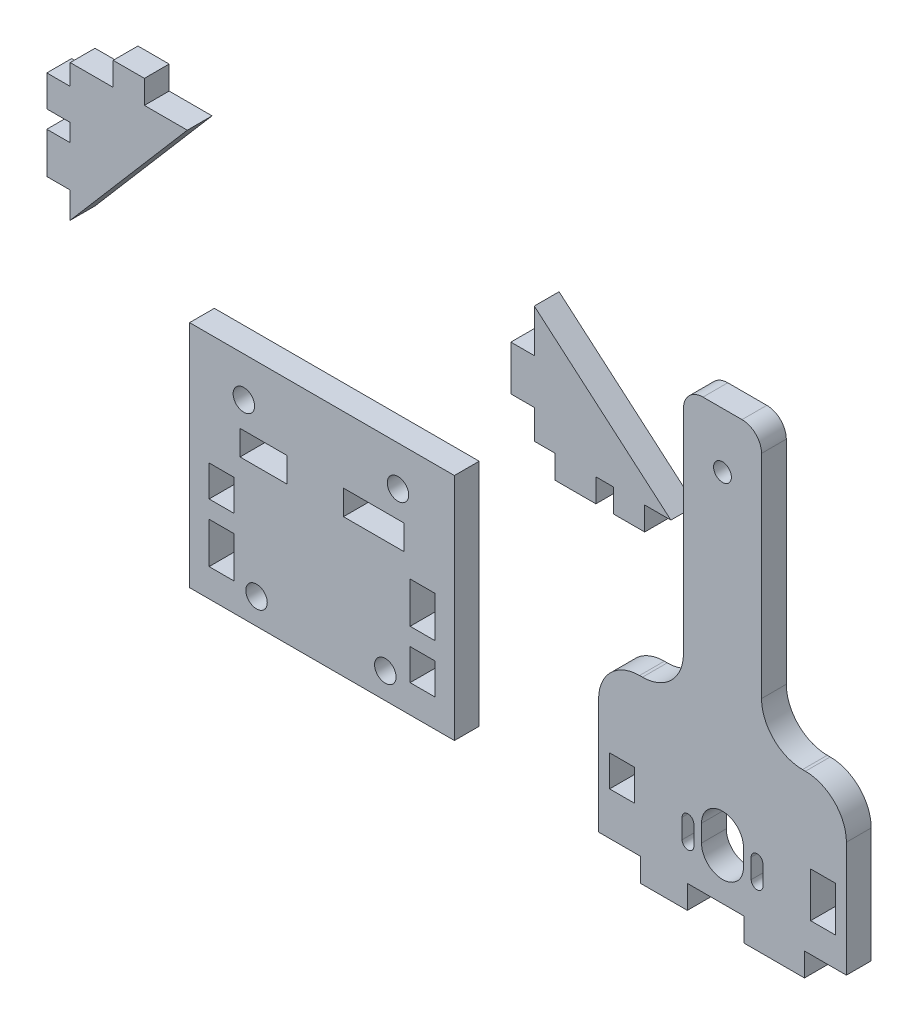
SolidWorks part; units mm, degrees
ref_plane "Front Plane" through (0, 0, 0) normal (0, 0, 1) x (1, 0, 0)
ref_plane "Top Plane" through (0, 0, 0) normal (0, 1, 0) x (1, 0, 0)
ref_plane "Right Plane" through (0, 0, 0) normal (1, 0, 0) x (0, 0, -1)
sketch "Model" plane through (0, 0, 0) normal (0, 0, 1) x (1, 0, 0)
  line L0 (46.0634, 150.8229) -> (46.0634, 142.8229)
  line L1 (46.0634, 138.3229) -> (46.0634, 127.8229)
  line L2 (52.0634, 156.1129) -> (52.0634, 150.8229)
  line L3 (52.0634, 142.8229) -> (52.0634, 138.3229)
  line L4 (52.0634, 127.8229) -> (52.0634, 121.1129)
  line L5 (63.0634, 162.1129) -> (63.0634, 156.1129)
  line L6 (52.0634, 121.1129) -> (82.0634, 156.1129)
  line L7 (71.0634, 156.1129) -> (71.0634, 162.1129)
  line L8 (71.6003, 124.5085) -> (71.6003, 132.5085)
  line L9 (86.6003, 129.5085) -> (86.6003, 124.5085)
  line L10 (87.649, 85.0685) -> (87.649, 77.0685)
  line L11 (87.649, 72.5685) -> (87.649, 62.0685)
  line L12 (93.999, 62.0685) -> (93.999, 72.5685)
  line L13 (93.999, 77.0685) -> (93.999, 85.0685)
  line L14 (95.574, 96.7035) -> (95.574, 90.3535)
  line L15 (198.1866, 47.05) -> (210.1866, 47.05)
  line L16 (224.6866, 47.05) -> (240.1866, 47.05)
  line L17 (187.4366, 53.05) -> (198.1866, 53.05)
  line L18 (210.1866, 53.05) -> (224.6866, 53.05)
  line L19 (240.1866, 53.05) -> (250.9366, 53.05)
  line L20 (107.574, 90.3535) -> (107.574, 96.7035)
  line L21 (63.2366, 54.8885) -> (169.9114, 54.8885)
  line L22 (248.1116, 60.55) -> (241.7616, 60.55)
  line L23 (87.649, 62.0685) -> (93.999, 62.0685)
  line L24 (139.149, 62.0685) -> (145.499, 62.0685)
  line L25 (190.2616, 64.05) -> (196.6116, 64.05)
  line L26 (145.499, 70.0685) -> (139.149, 70.0685)
  line L27 (248.1116, 72.05) -> (241.7616, 72.05)
  line L28 (196.6116, 72.05) -> (190.2616, 72.05)
  line L29 (93.999, 72.5685) -> (87.649, 72.5685)
  line L30 (145.499, 74.5685) -> (139.149, 74.5685)
  line L31 (122.074, 96.7035) -> (122.074, 90.3535)
  line L32 (87.649, 77.0685) -> (93.999, 77.0685)
  line L33 (145.499, 85.0685) -> (139.149, 85.0685)
  line L34 (93.999, 85.0685) -> (87.649, 85.0685)
  line L35 (129.624, 124.2585) -> (129.624, 131.2585)
  line L36 (137.574, 90.3535) -> (137.574, 96.7035)
  line L37 (139.149, 70.0685) -> (139.149, 62.0685)
  line L38 (139.149, 74.5685) -> (139.149, 85.0685)
  line L39 (95.574, 90.3535) -> (107.574, 90.3535)
  line L40 (122.074, 90.3535) -> (137.574, 90.3535)
  line L41 (240.4366, 93.05) -> (239.6866, 93.05)
  line L42 (198.6866, 93.05) -> (197.9366, 93.05)
  line L43 (140.624, 133.2585) -> (140.624, 124.2585)
  line L44 (145.499, 62.0685) -> (145.499, 70.0685)
  line L45 (145.499, 74.5685) -> (145.499, 85.0685)
  line L46 (137.574, 96.7035) -> (122.074, 96.7035)
  line L47 (107.574, 96.7035) -> (95.574, 96.7035)
  line L48 (164.9642, 139.0399) -> (164.9642, 150.5399)
  line L49 (140.624, 124.2585) -> (129.624, 124.2585)
  line L50 (86.6003, 124.5085) -> (71.6003, 124.5085)
  line L51 (176.2542, 125.5399) -> (186.7542, 125.5399)
  line L52 (191.2542, 125.5399) -> (199.2542, 125.5399)
  line L53 (170.9642, 161.5399) -> (170.9642, 150.5399)
  line L54 (170.9642, 139.0399) -> (170.9642, 131.5399)
  line L55 (176.2542, 131.5399) -> (176.2542, 125.5399)
  line L56 (46.0634, 127.8229) -> (52.0634, 127.8229)
  line L57 (170.9642, 131.5399) -> (176.2542, 131.5399)
  line L58 (186.7542, 131.5399) -> (191.2542, 131.5399)
  line L59 (199.2542, 131.5399) -> (205.9642, 131.5399)
  line L60 (71.6003, 132.5085) -> (83.6003, 132.5085)
  line L61 (131.624, 133.2585) -> (140.624, 133.2585)
  line L62 (186.7542, 131.5399) -> (186.7542, 125.5399)
  line L63 (187.4366, 82.55) -> (187.4366, 53.05)
  line L64 (190.2616, 72.05) -> (190.2616, 64.05)
  line L65 (191.2542, 131.5399) -> (191.2542, 125.5399)
  line L66 (52.0634, 138.3229) -> (46.0634, 138.3229)
  line L67 (170.9642, 139.0399) -> (164.9642, 139.0399)
  line L68 (46.0634, 142.8229) -> (52.0634, 142.8229)
  line L69 (196.6116, 64.05) -> (196.6116, 72.05)
  line L70 (198.1866, 53.05) -> (198.1866, 47.05)
  line L71 (199.2542, 125.5399) -> (199.2542, 131.5399)
  line L72 (170.9642, 150.5399) -> (164.9642, 150.5399)
  line L73 (52.0634, 150.8229) -> (46.0634, 150.8229)
  line L74 (82.0634, 156.1129) -> (71.0634, 156.1129)
  line L75 (63.0634, 156.1129) -> (52.0634, 156.1129)
  line L76 (208.8366, 67.05) -> (208.8366, 62.05)
  line L77 (209.1866, 157.95) -> (209.1866, 103.55)
  line L78 (210.1866, 47.05) -> (210.1866, 53.05)
  line L79 (211.8366, 62.05) -> (211.8366, 67.05)
  line L80 (71.0634, 162.1129) -> (63.0634, 162.1129)
  line L81 (224.1866, 162.95) -> (214.1866, 162.95)
  line L82 (205.9642, 131.5399) -> (170.9642, 161.5399)
  line L83 (212.8116, 68.2) -> (212.8116, 63.8)
  line L84 (224.6866, 53.05) -> (224.6866, 47.05)
  line L85 (225.5616, 63.8) -> (225.5616, 68.2)
  line L86 (226.5366, 67.05) -> (226.5366, 62.05)
  line L87 (229.1866, 103.55) -> (229.1866, 157.95)
  line L88 (229.5366, 62.05) -> (229.5366, 67.05)
  line L89 (240.1866, 47.05) -> (240.1866, 53.05)
  line L90 (241.7616, 60.55) -> (241.7616, 72.05)
  line L91 (248.1116, 60.55) -> (248.1116, 72.05)
  line L92 (250.9366, 53.05) -> (250.9366, 82.55)
  arc A0 (169.9114, 54.8885) -> (63.2366, 54.8885) centre (116.574, 92.0385) ccw
  arc A1 (229.1866, 103.55) -> (239.6866, 93.05) centre (239.6866, 103.55) ccw
  arc A2 (250.9366, 82.55) -> (240.4366, 93.05) centre (240.4366, 82.55) ccw
  arc A3 (197.9366, 93.05) -> (187.4366, 82.55) centre (197.9366, 82.55) ccw
  arc A4 (198.6866, 93.05) -> (209.1866, 103.55) centre (198.6866, 103.55) ccw
  arc A5 (225.5616, 68.2) -> (212.8116, 68.2) centre (219.1866, 68.2) ccw
  arc A6 (212.8116, 63.8) -> (225.5616, 63.8) centre (219.1866, 63.8) ccw
  arc A7 (214.1866, 162.95) -> (209.1866, 157.95) centre (214.1866, 157.95) ccw
  arc A8 (229.1866, 157.95) -> (224.1866, 162.95) centre (224.1866, 157.95) ccw
  arc A9 (86.6003, 129.5085) -> (83.6003, 132.5085) centre (83.6003, 129.5085) ccw
  circle A10 centre (219.1866, 148.81) radius 2.285
  circle A11 centre (78.574, 66.1385) radius 2.2
  circle A12 centre (154.574, 66.1385) radius 2.2
  circle A13 centre (83.574, 117.8885) radius 2.2
  circle A14 centre (149.574, 117.8885) radius 2.2
  arc A15 (131.624, 133.2585) -> (129.624, 131.2585) centre (131.624, 131.2585) ccw
  arc A16 (226.5366, 62.05) -> (229.5366, 62.05) centre (228.0366, 62.05) ccw
  arc A17 (229.5366, 67.05) -> (226.5366, 67.05) centre (228.0366, 67.05) ccw
  arc A18 (208.8366, 62.05) -> (211.8366, 62.05) centre (210.3366, 62.05) ccw
  arc A19 (211.8366, 67.05) -> (208.8366, 67.05) centre (210.3366, 67.05) ccw
extrude "Boss-Extrude1" add sketch "Model" along normal blind 6.35
sketch "Sketch2" plane through (0, 0, 6.35) normal (0, 0, 1) x (1, 0, 0)
  line L0 (219.1866, 68.2) -> (219.1866, 63.8) construction
  line L1 (224.5616, 68.2) -> (224.5616, 63.8)
  line L2 (213.8116, 68.2) -> (213.8116, 63.8)
  line L3 (225.5616, 63.8) -> (225.5616, 68.2) construction
  line L4 (219.1866, 68.2) -> (219.1866, 63.8) construction
  line L5 (226.1415, 68.2) -> (226.1415, 63.8)
  line L6 (212.2318, 68.2) -> (212.2318, 63.8)
  arc A0 (224.5616, 68.2) -> (213.8116, 68.2) centre (219.1866, 68.2) ccw
  arc A1 (213.8116, 63.8) -> (224.5616, 63.8) centre (219.1866, 63.8) ccw
  arc A2 (226.1415, 68.2) -> (212.2318, 68.2) centre (219.1866, 68.2) ccw
  arc A3 (212.2318, 63.8) -> (226.1415, 63.8) centre (219.1866, 63.8) ccw
  point P4 (219.1866, 66)
  point P13 (219.1866, 66)
  dimension "D1" = 1
extrude "Boss-Extrude2" add sketch "Sketch2" against normal up to surface (6.35 mm away) up to face at (244.9366, 66.3, 0)
sketch "Sketch4" plane through (0, 0, 6.35) normal (0, 0, 1) x (1, 0, 0)
  line L0 (63.2366, 54.8885) -> (169.9114, 54.8885) construction
  line L2 (82.649, 54.8885) -> (82.649, 113.7035)
  line L3 (82.649, 113.7035) -> (150.499, 113.7035)
  line L4 (150.499, 54.8885) -> (150.499, 113.7035)
  line L5 (87.649, 72.5685) -> (87.649, 62.0685) construction
  line L6 (145.499, 62.0685) -> (145.499, 70.0685) construction
  line L7 (137.574, 96.7035) -> (122.074, 96.7035) construction
  line L8 (82.649, 54.8885) -> (31.6701, 45.7244)
  line L9 (31.6701, 45.7244) -> (55.3205, 121.4654)
  line L10 (55.3205, 121.4654) -> (94.6879, 166.8203)
  line L11 (94.6879, 166.8203) -> (153.5145, 163.0781)
  line L12 (153.5145, 163.0781) -> (161.8969, 140.7749)
  line L13 (161.8969, 140.7749) -> (181.2064, 118.0227)
  line L14 (181.2064, 118.0227) -> (187.5485, 101.148)
  line L15 (187.5485, 101.148) -> (177.4642, 45.7244)
  line L16 (177.4642, 45.7244) -> (150.499, 54.8885)
  dimension "D1" = 5
  dimension "D2" = 5
  dimension "D3" = 17
extrude "Cut-Extrude2" cut sketch "Sketch4" against normal blind 10
sketch "Sketch5" plane through (0, 0, 6.35) normal (0, 0, 1) x (1, 0, 0)
  line L0 (82.649, 61.5062) -> (150.499, 61.5062) construction
  line L1 (82.649, 54.8885) -> (82.649, 113.7035) construction
  line L2 (150.499, 113.7035) -> (150.499, 54.8885) construction
  line L3 (82.649, 103.5062) -> (150.499, 103.5062) construction
  line L4 (136.0486, 103.5062) -> (136.0486, 61.5062) construction
  circle A0 centre (99.7986, 61.5062) radius 2.75
  circle A1 centre (132.7986, 61.5062) radius 2.75
  circle A2 centre (96.5486, 103.5062) radius 2.75
  circle A3 centre (136.0486, 103.5062) radius 2.75
  point P16 (136.391, 104.1909)
  point P18 (135.0216, 103.9341)
  point P19 (136.0486, 103.5062)
  dimension "D1" = 5.5
  dimension "D2" = 5.5
  dimension "D4" = 5.5
  dimension "D5" = 5.5
  dimension "D3" = 33
  dimension "D6" = 39.5
  dimension "D7" = 42
  dimension "D8" = 3.25
extrude "Cut-Extrude3" cut sketch "Sketch5" against normal blind 10
sketch "Sketch6" plane through (0, 0, 6.35) normal (0, 0, 1) x (1, 0, 0)
  line L1 (42.8966, 167.7184) -> (253.804, 167.7184)
  line L2 (42.8966, 167.7184) -> (42.8966, 43.3294)
  line L3 (42.8966, 43.3294) -> (253.804, 43.3294)
  line L4 (253.804, 167.7184) -> (253.804, 43.3294)
